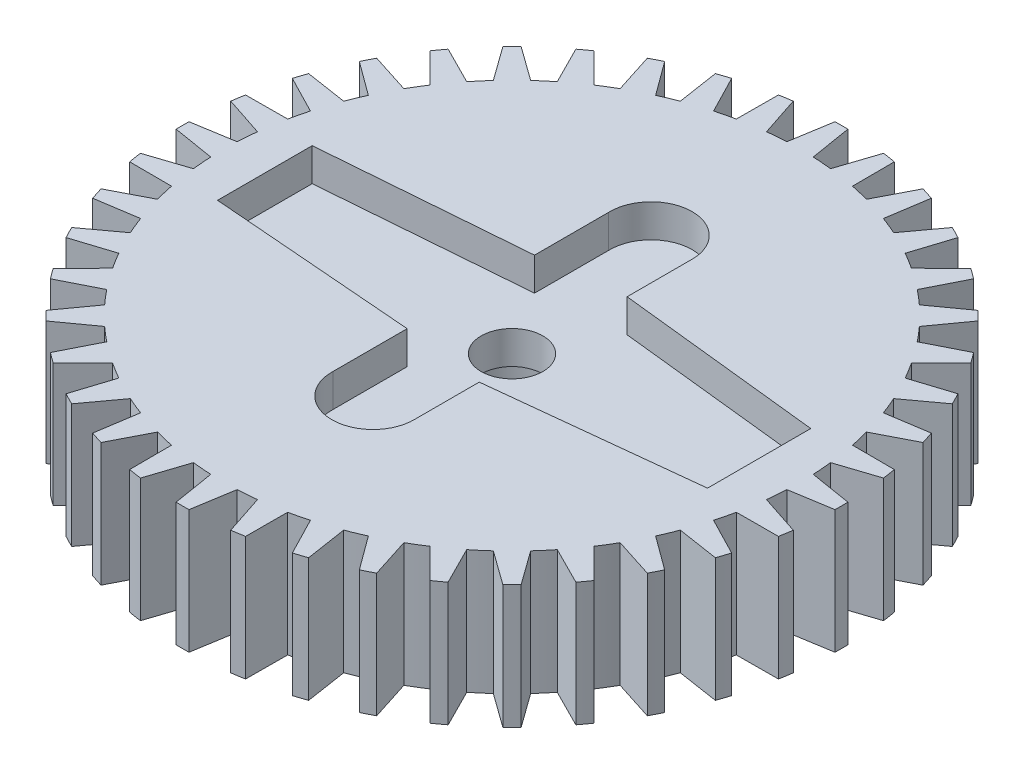
SolidWorks part; units mm, degrees
ref_plane "Front Plane" through (0, 0, 0) normal (0, 0, 1) x (1, 0, 0)
ref_plane "Top Plane" through (0, 0, 0) normal (0, 1, 0) x (1, 0, 0)
ref_plane "Right Plane" through (0, 0, 0) normal (1, 0, 0) x (0, 0, -1)
sketch "Sketch1" plane through (0, 0, 0) normal (0, 1, 0) x (1, 0, 0)
  circle A0 centre (0, 0) radius 1.5
  circle A1 centre (0, 0) radius 16
  dimension "D1" = 3
  dimension "D2" = 32
extrude "Boss-Extrude1" add sketch "Sketch1" along normal blind 6
sketch "Sketch2" plane through (0, 6, 0) normal (0, 1, 0) x (1, 0, 0)
  line L0 (0, 0) -> (0, 15.5) construction
  line L1 (0, 0) -> (-0.3141, 15.9969) construction
  line L2 (0, 0) -> (-0.6412, 13.9853) construction
  line L3 (0, 0) -> (-1.0984, 13.9568) construction
  line L4 (-0.6412, 13.9853) -> (-0.3141, 15.9969)
  line L5 (0.6412, 13.9853) -> (0.3141, 15.9969)
  line L6 (-1.0984, 13.9568) -> (-1.346, 17.1025)
  line L7 (-1.346, 17.1025) -> (1.346, 17.1025)
  line L8 (1.346, 17.1025) -> (1.0984, 13.9568)
  circle A0 centre (0, 0) radius 16 construction
  arc A1 (0.3141, 15.9969) -> (-0.3141, 15.9969) centre (0, 0) ccw
  arc A3 (-0.6412, 13.9853) -> (-1.0984, 13.9568) centre (0, 0) ccw
  arc A4 (0.6412, 13.9853) -> (1.0984, 13.9568) centre (0, 0) cw
  dimension "D4" = 14
  dimension "D1" = 1.125
  dimension "D2" = 1.5
  dimension "D3" = 1.875
extrude "Cut-Extrude1" cut sketch "Sketch2" against normal up to next (6 mm away)
pattern_circular "CirPattern1" count 40 over 360 about axis through (0, 6, 0) along (0, -1, 0) of "Cut-Extrude1" reverse direction yes
sketch "Sketch3" plane through (0, 6, 0) normal (0, 1, 0) x (1, 0, 0)
  line L0 (15.75, 0) -> (-15.75, 0) construction
  line L1 (0, -6.75) -> (0, 6.75) construction
  line L2 (-1.8988, 6.6833) -> (-1.8988, 3) construction
  line L3 (1.8988, 6.6833) -> (1.8988, 3.5) construction
  line L4 (-15.75, 1.9) -> (-1.8988, 3) construction
  line L5 (15.7506, 2) -> (1.8988, 3.5) construction
  line L6 (15.7506, -2) -> (1.8988, -3.5) construction
  line L7 (1.8988, -6.6833) -> (1.8988, -3.5) construction
  line L8 (-1.8988, -6.6833) -> (-1.8988, -3) construction
  line L9 (-15.75, -1.9) -> (-1.8988, -3) construction
  line L10 (-1.9988, 6.6816) -> (-1.9988, 3.0924)
  line L11 (-15.754, 2) -> (-1.9988, 3.0924)
  line L12 (-15.754, -2) -> (-1.9988, -3.0924)
  line L13 (-1.9988, -6.6816) -> (-1.9988, -3.0924)
  line L14 (1.9988, -6.6816) -> (1.9988, -3.5898)
  line L15 (15.7561, -2.1) -> (1.9988, -3.5898)
  line L16 (15.7561, 2.1) -> (1.9988, 3.5898)
  line L17 (1.9988, 6.6816) -> (1.9988, 3.5898)
  line L18 (-12, 2.2981) -> (-12, -2.2981)
  line L19 (12, 2.5067) -> (12, -2.5067)
  circle A0 centre (0, 0) radius 1.25
  arc A1 (-1.8988, 6.6833) -> (1.8988, 6.6833) centre (0, 6.75) cw construction
  arc A2 (-15.75, 1.9) -> (-15.75, -1.9) centre (-15.75, 0) ccw construction
  arc A3 (15.7506, 2) -> (15.7506, -2) centre (15.75, 0) cw construction
  arc A4 (-1.8988, -6.6833) -> (1.8988, -6.6833) centre (0, -6.75) ccw construction
  arc A5 (-15.754, 2) -> (-15.754, -2) centre (-15.75, 0) ccw
  arc A6 (-1.9988, -6.6816) -> (1.9988, -6.6816) centre (0, -6.75) ccw
  arc A7 (15.7561, 2.1) -> (15.7561, -2.1) centre (15.75, 0) cw
  arc A8 (-1.9988, 6.6816) -> (1.9988, 6.6816) centre (0, 6.75) cw
  point P5 (0, 0)
  point P8 (0, 0)
  dimension "D1" = 2.5
  dimension "D4" = 1.9
  dimension "D5" = 1.9
  dimension "D11" = 2
  dimension "D2" = 13.5
  dimension "D3" = 31.5
  dimension "D6" = 1.1
  dimension "D8" = 6
  dimension "D9" = 7
  dimension "D10" = 3.5
  dimension "D12" = 12
  dimension "D13" = 12
  dimension "D7" = 0.1
extrude "Cut-Extrude2" cut sketch "Sketch3" against normal blind 1.6 contours A8 L10 L11 A5 L12 L13 A6 L14 L15 A7 L16 L17 A4 L8 L9 A2 L4 L2 A1 L3 L5 A3 L6 L7 | L8 A4 L7 L6 A3 L5 L3 A1 L2 L4 A2 L9 A0 region at (0, 6, -8.453)
sketch "Sketch4" plane through (0, 0, 0) normal (0, -1, 0) x (1, 0, 0)
  circle A0 centre (0, 0) radius 2.6
  dimension "D1" = 5.2
extrude "Cut-Extrude3" cut sketch "Sketch4" against normal offset from surface (2.8 mm away) 1.6 up to face at (0, 4.4, 1.5)
equation "\"num_teeth\" = 40"
equation "\"D1@Sketch2\"=(1.5/6)*(360 / \"num_teeth\")*0.5"
equation "\"D2@Sketch2\"=(2/6)*(360 / \"num_teeth\")*0.5"
equation "\"D3@Sketch2\"=(2.5/6)*(360 / \"num_teeth\")*0.5"
equation "\"D1@CirPattern1\"=\"num_teeth\""
equation "\"diameter\" = 30mm"
equation "\"D2@Sketch1\"=\"diameter\" + 2"
equation "\"D4@Sketch2\"=(\"diameter\" / 2) - 1"
